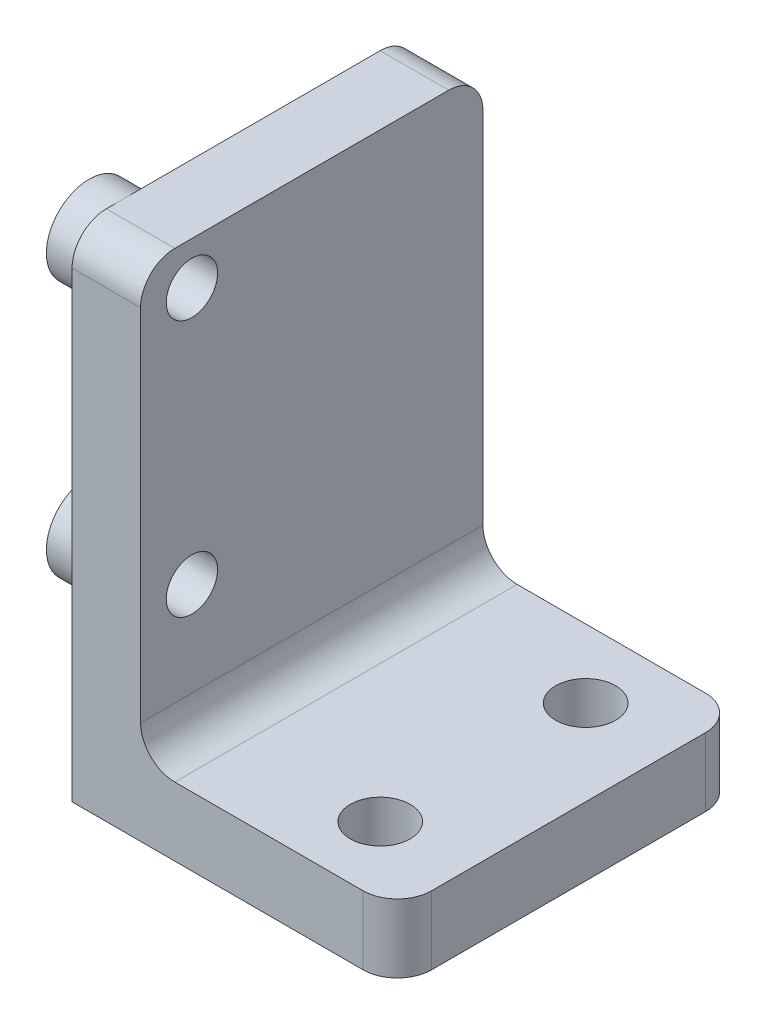
SolidWorks part; units mm, degrees
ref_plane "Front Plane" through (0, 0, 0) normal (0, 0, 1) x (1, 0, 0)
ref_plane "Top Plane" through (0, 0, 0) normal (0, 1, 0) x (1, 0, 0)
ref_plane "Right Plane" through (0, 0, 0) normal (1, 0, 0) x (0, 0, -1)
sketch "Sketch1" plane through (0, 0, 0) normal (0, 0, 1) x (1, 0, 0)
  line L0 (0, 0) -> (0, 29)
  line L1 (0, 29) -> (4, 29)
  line L2 (4, 29) -> (4, 4)
  line L3 (4, 4) -> (19, 4)
  line L4 (19, 4) -> (19, 0)
  line L5 (19, 0) -> (0, 0)
  dimension "D1" = 4
  dimension "D2" = 4
  dimension "D3" = 25
  dimension "D4" = 15
extrude "Boss-Extrude1" add sketch "Sketch1" along normal blind 20
sketch "Sketch2" plane through (0, 0, 0) normal (-1, 0, 0) x (0, 0, 1)
  line L0 (20, 29) -> (0, 29) construction
  line L1 (20, 29) -> (20, 0) construction
  circle A0 centre (17, 26.5) radius 1.5
  circle A1 centre (17, 11.5) radius 1.5
  dimension "D2" = 3
  dimension "D1" = 15
  dimension "D3" = 2.5
  dimension "D4" = 3
extrude "Cut-Extrude1" cut sketch "Sketch2" against normal through all
sketch "Sketch3" plane through (0, 4, 0) normal (0, 1, 0) x (1, 0, 0)
  line L0 (19, -20) -> (19, 0) construction
  circle A0 centre (14, -4) radius 1.75
  circle A1 centre (14, -16) radius 1.75
  point P6 (19, -10)
  dimension "D1" = 3.5
  dimension "D2" = 3.5
  dimension "D3" = 12
  dimension "D4" = 6
  dimension "D5" = 5
extrude "Cut-Extrude2" cut sketch "Sketch3" against normal through all
fillet "Fillet1" radius 2 5 edges at (19, 2, 0) (19, 2, 20) (4, 4, 10) (2, 29, 0) (2, 29, 20)
sketch "Sketch4" plane through (4, 0, 0) normal (1, 0, 0) x (0, 0, -1)
  line L0 (-18, 29) -> (-2, 29) construction
  circle A0 centre (-17, 26.5) radius 2.5
  circle A1 centre (-17, 11.5) radius 2.5
  circle A2 centre (-17, 11.5) radius 1.5 construction
  circle A3 centre (-17, 26.5) radius 1.5 construction
  circle A4 centre (-17, 11.5) radius 1.5
  circle A5 centre (-17, 26.5) radius 1.5
extrude "Boss-Extrude2" add sketch "Sketch4" against normal blind 2 from surface starting at face at (0, 25, 17)
